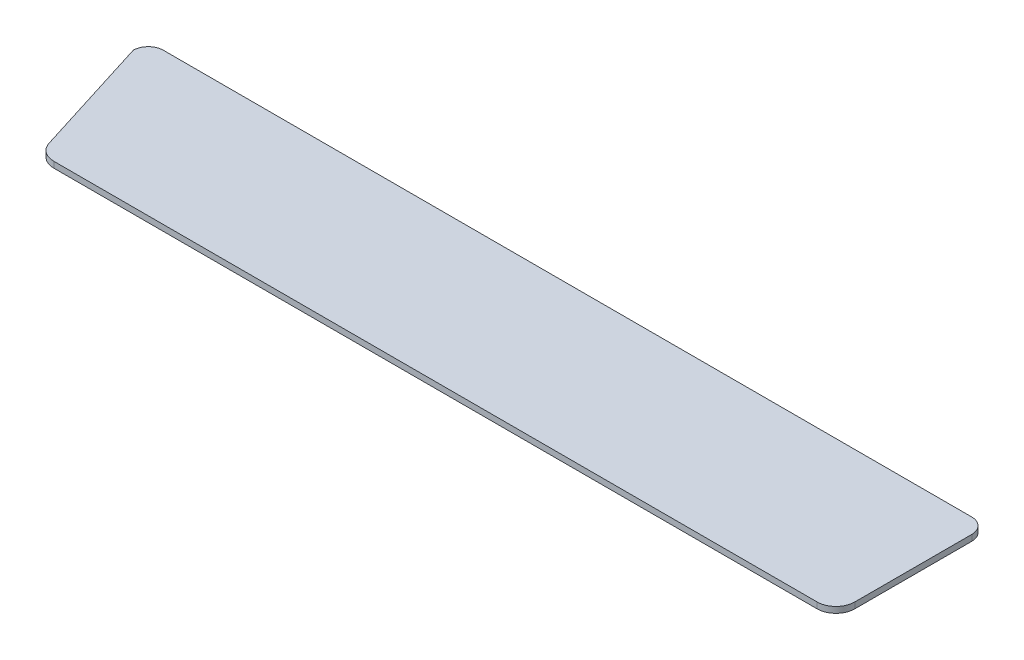
SolidWorks part; units mm, degrees
ref_plane "Front" through (0, 0, 0) normal (0, 0, 1) x (1, 0, 0)
ref_plane "Top" through (0, 0, 0) normal (0, 1, 0) x (1, 0, 0)
ref_plane "Right" through (0, 0, 0) normal (1, 0, 0) x (0, 0, -1)
sketch "Sketch1" plane through (0, 0, 0) normal (0, 1, 0) x (1, 0, 0)
  line L0 (0, 142) -> (42, 8)
  line L1 (0, 0) -> (444.5, 0)
  line L2 (0, 0) -> (0, 150)
  line L3 (0, 150) -> (444.5, 150)
  line L4 (444.5, 0) -> (444.5, 150)
  circle A0 centre (8, 142) radius 8
  circle A1 centre (50, 8) radius 8
  circle A2 centre (436.5, 142) radius 8
  circle A3 centre (436.5, 8) radius 8
  dimension "D3" = 8
  dimension "D5" = 8
  dimension "D7" = 8
  dimension "D9" = 8
  dimension "D1" = 150
  dimension "D2" = 444.5
  dimension "D4" = 8
  dimension "D6" = 50
  dimension "D8" = 8
  dimension "D10" = 8
extrude "Boss-Extrude1" add sketch "Sketch1" along normal blind 3.175 contours A3 L4 A2 L3 A0 L0 A1 L1 | A1 | A0 L0 | A2 | A3 region at (8.0436, 0, -142.0137) region at (232.5322, 0, -76.3847) region at (50, 0, -8) region at (436.5, 0, -142) region at (436.5, 0, -8)
sketch "Sketch2" plane through (0, 0, 0) normal (0, 0, 1) x (1, 0, 0)
  line L1 (-78.5546, 38.0306) -> (518.9117, 38.0306)
  line L2 (-78.5546, 38.0306) -> (-78.5546, -22.9419)
  line L3 (-78.5546, -22.9419) -> (518.9117, -22.9419)
  line L4 (518.9117, 38.0306) -> (518.9117, -22.9419)
extrude "Cut-Extrude1" cut sketch "Sketch2" against normal blind 70
fillet "Fillet1" radius 10 1 edges at (22.5672, 1.5875, -70)
fillet "Fillet2" radius 10 1 edges at (444.5, 1.5875, -70)
